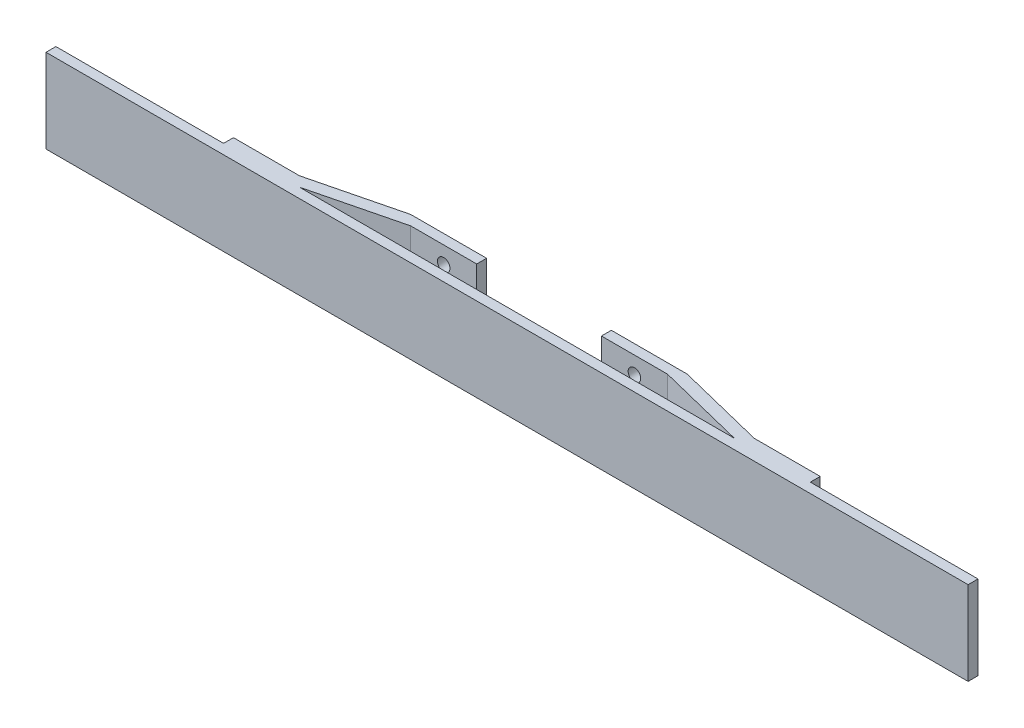
SolidWorks part; units mm, degrees
material "ABS"
ref_plane "Front Plane" through (0, 0, 0) normal (0, 0, 1) x (1, 0, 0)
ref_plane "Top Plane" through (0, 0, 0) normal (0, 1, 0) x (1, 0, 0)
ref_plane "Right Plane" through (0, 0, 0) normal (1, 0, 0) x (0, 0, -1)
sketch "Sketch1" plane through (0, 0, 0) normal (0, 0, 1) x (1, 0, 0)
  line L1 (-26.033, 10.5636) -> (278.767, 10.5636)
  line L2 (-26.033, 10.5636) -> (-26.033, -14.8364)
  line L3 (-26.033, -14.8364) -> (278.767, -14.8364)
  line L4 (278.767, 10.5636) -> (278.767, -14.8364)
  dimension "D1" = 25.4
  dimension "D2" = 304.8
extrude "Boss-Extrude2" add sketch "Sketch1" along normal blind 12.7 contours L1 L4 L3 L2
fillet "Fillet1" radius 12.7 2 edges at (-26.033, -2.1364, 12.7) (278.767, -2.1364, 12.7)
sketch "Sketch6" plane through (0, 10.5636, 0) normal (0, 1, 0) x (1, 0, 0)
  line L5 (-23.033, 0) -> (275.767, 0)
  line L6 (-13.333, -9.7) -> (266.067, -9.7)
  line L7 (-13.333, -9.7) -> (266.067, -9.7)
  arc A8 (266.067, -9.7) -> (275.767, 0) centre (266.067, 0) ccw
  arc A9 (-23.033, 0) -> (-13.333, -9.7) centre (-13.333, 0) ccw
  arc A10 (266.067, -9.7) -> (275.767, 0) centre (266.067, 0) ccw
  arc A11 (-23.033, 0) -> (-13.333, -9.7) centre (-13.333, 0) ccw
  dimension "D1" = 3
extrude "Cut-Extrude3" cut sketch "Sketch6" against normal through all
sketch "Sketch8" plane through (0, 0, 9.7) normal (0, 0, -1) x (-1, 0, 0)
  line L0 (13.333, 10.5636) -> (-266.067, 10.5636) construction
  line L1 (-145.267, 10.5636) -> (-215.267, 10.5636)
  line L2 (-145.267, 10.5636) -> (-145.267, -14.8364)
  line L3 (-145.267, -14.8364) -> (-215.267, -14.8364)
  line L4 (-215.267, 10.5636) -> (-215.267, -14.8364)
  line L5 (13.333, -14.8364) -> (-266.067, -14.8364) construction
  line L6 (-266.067, -14.8364) -> (-266.067, 10.5636) construction
  line L7 (-37.467, 10.5636) -> (-107.467, 10.5636)
  line L8 (-37.467, 10.5636) -> (-37.467, -14.8364)
  line L9 (-37.467, -14.8364) -> (-107.467, -14.8364)
  line L10 (-107.467, 10.5636) -> (-107.467, -14.8364)
  line L11 (13.333, -14.8364) -> (13.333, 10.5636) construction
  dimension "D1" = 50.8
  dimension "D2" = 70
  dimension "D3" = 50.8
  dimension "D4" = 70
extrude "Boss-Extrude3" add sketch "Sketch8" along normal blind 9.7
sketch "Sketch9" plane through (0, 10.5636, 0) normal (0, 1, 0) x (1, 0, 0)
  line L0 (145.267, -9.7) -> (165.267, -9.7)
  line L1 (165.267, -9.7) -> (192.267, -9.7)
  line L2 (192.267, -9.7) -> (165.267, -3)
  line L3 (165.267, -3) -> (145.267, -3)
  line L4 (145.267, 0) -> (145.267, -9.7) construction
  line L5 (145.267, -3) -> (145.267, -9.7)
  line L6 (145.267, 0) -> (215.267, 0) construction
  line L7 (215.267, -6.7) -> (195.267, -6.7)
  line L8 (215.267, 0) -> (215.267, -9.7) construction
  line L9 (195.267, -6.7) -> (168.267, 0)
  line L10 (168.267, 0) -> (215.267, 0)
  line L11 (215.267, 0) -> (215.267, -6.7)
  dimension "D1" = 3
  dimension "D2" = 20
  dimension "D3" = 27
  dimension "D4" = 20
  dimension "D5" = 20
  dimension "D6" = 3
  dimension "D7" = 47
extrude "Cut-Extrude4" cut sketch "Sketch9" against normal through all
sketch "Sketch12" plane through (0, 10.5636, 0) normal (0, 1, 0) x (1, 0, 0)
  line L0 (107.467, -9.7) -> (107.467, -3)
  line L1 (107.467, 0) -> (107.467, -9.7) construction
  line L2 (107.467, -3) -> (87.467, -3)
  line L3 (87.467, -3) -> (60.467, -9.7)
  line L4 (60.467, -9.7) -> (107.467, -9.7)
  line L11 (37.467, -6.7) -> (57.467, -6.7)
  line L12 (37.467, 0) -> (37.467, -9.7) construction
  line L13 (57.467, -6.7) -> (84.467, 0)
  line L14 (37.467, 0) -> (107.467, 0) construction
  line L15 (84.467, 0) -> (37.467, 0)
  line L16 (37.467, 0) -> (37.467, -6.7)
  dimension "D1" = 3
  dimension "D2" = 20
  dimension "D3" = 47
  dimension "D4" = 3
  dimension "D5" = 20
  dimension "D6" = 47
extrude "Cut-Extrude5" cut sketch "Sketch12" against normal through all
sketch "Sketch13" plane through (0, 0, 12.7) normal (0, 0, 1) x (1, 0, 0)
  line L1 (-13.333, -14.8364) -> (-26.033, -14.8364)
  line L2 (-13.333, -14.8364) -> (-13.333, 10.5636)
  line L3 (-13.333, 10.5636) -> (-26.033, 10.5636)
  line L4 (-26.033, -14.8364) -> (-26.033, 10.5636)
  line L5 (266.067, -14.8364) -> (278.767, -14.8364)
  line L6 (266.067, -14.8364) -> (266.067, 10.5636)
  line L7 (266.067, 10.5636) -> (278.767, 10.5636)
  line L8 (278.767, -14.8364) -> (278.767, 10.5636)
extrude "Cut-Extrude7" cut sketch "Sketch13" against normal through all
sketch "Sketch14" plane through (0, 0, 3) normal (0, 0, 1) x (1, 0, 0)
  line L0 (97.467, -14.8364) -> (97.467, 10.5636) construction
  line L1 (107.467, -14.8364) -> (87.467, -14.8364) construction
  line L2 (107.467, 10.5636) -> (87.467, 10.5636) construction
  line L3 (107.467, -2.1364) -> (87.467, -2.1364) construction
  line L4 (107.467, -14.8364) -> (107.467, 10.5636) construction
  line L5 (87.467, -14.8364) -> (87.467, 10.5636) construction
  point P12 (97.467, 5.3636)
  point P13 (97.467, -9.6364)
  point P14 (0, 0)
  dimension "D1" = 7.5
hole_wizard "#6 Clearance Hole1" positions "Sketch15" profile "Sketch16" hole size "#6" standard "ANSI Inch" end condition up to next
sketch "Sketch15" plane through (0, 0, 3) normal (0, 0, 1) x (1, 0, 0)
  line L0 (107.467, -2.1364) -> (145.267, -2.1364) construction
  line L1 (145.267, -14.8364) -> (145.267, 10.5636) construction
  line L3 (126.367, -2.1364) -> (126.367, 16.7203) construction
  point P0 (97.467, 5.3636)
  point P2 (97.467, -9.6364)
  point P22 (155.267, -9.6364)
  point P23 (155.267, 5.3636)
sketch "Sketch16" plane through (97.467, 5.3636, 3) normal (1, 0, 0) x (0, -1, 0)
  line L0 (0, 0) -> (0, 3)
  line L1 (0, 3) -> (1.8986, 3)
  line L2 (1.8986, 3) -> (1.8986, 0)
  line L5 (1.8986, 0) -> (0, 0)
  line L11 (0, -6.35) -> (0, 107.95) construction
  dimension "Thru Hole Dia." = 3.7973
  dimension "Thru Hole Depth" = 3
